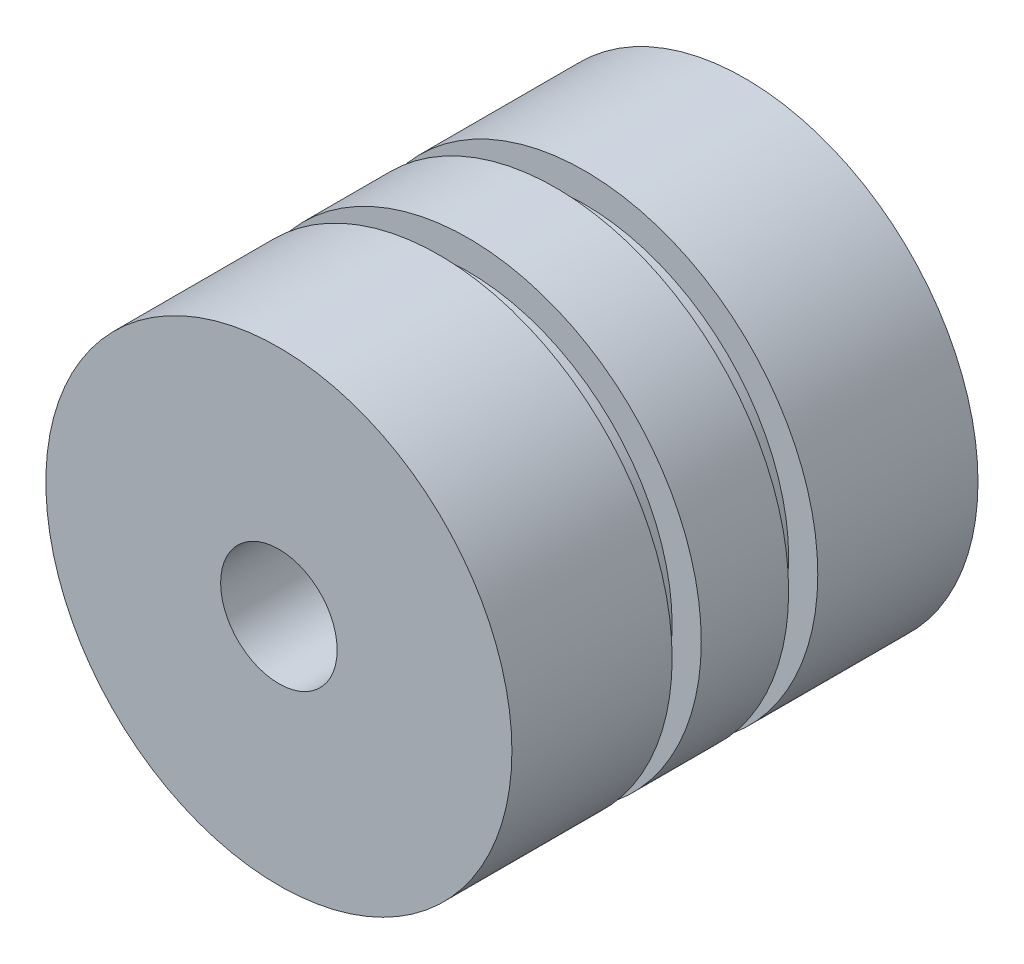
SolidWorks part; units mm, degrees
ref_plane "정면" through (0, 0, 0) normal (0, 0, 1) x (1, 0, 0)
ref_plane "윗면" through (0, 0, 0) normal (0, 1, 0) x (1, 0, 0)
ref_plane "우측면" through (0, 0, 0) normal (1, 0, 0) x (0, 0, -1)
sketch "스케치1" plane through (0, 0, 0) normal (0, 0, 1) x (1, 0, 0)
  circle A0 centre (0, 0) radius 16
  circle A1 centre (0, 0) radius 4
  dimension "D1" = 8
  dimension "D2" = 32
extrude "보스-돌출1" add sketch "스케치1" along normal mid plane 32
sketch "스케치2" plane through (0, 0, 0) normal (0, 0, 1) x (1, 0, 0)
  circle A0 centre (0, 0) radius 14
  circle A1 centre (0, 0) radius 16
  circle A2 centre (0, 0) radius 16 construction
  dimension "D1" = 28
extrude "컷-돌출1" cut sketch "스케치2" against normal blind 2 from offset 5
extrude "컷-돌출2" cut sketch "스케치2<2>" against normal blind 2 from offset 3 offset against normal yes
sketch "스케치2<2>" plane through (0, 0, 0) normal (0, 0, 1) x (1, 0, 0) same geometry as "스케치2"
sketch "스케치4" plane through (0, 0, -16) normal (0, 0, -1) x (-1, 0, 0)
  circle A0 centre (0, 0) radius 5.45
  dimension "D1" = 10.9
extrude "컷-돌출4" cut sketch "스케치4" against normal blind 10
